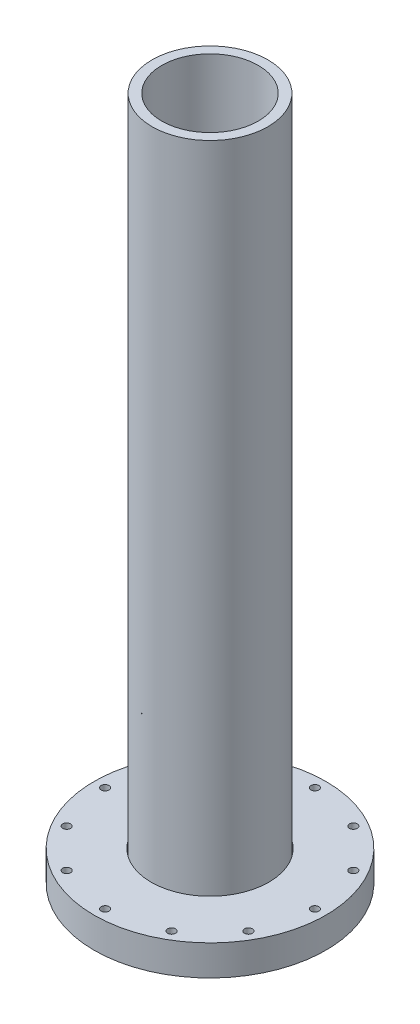
SolidWorks part; units mm, degrees
material "AISI 316 Stainless Steel Sheet (SS)"
ref_plane "Front Plane" through (0, 0, 0) normal (0, 0, 1) x (1, 0, 0)
ref_plane "Top Plane" through (0, 0, 0) normal (0, 1, 0) x (1, 0, 0)
ref_plane "Right Plane" through (0, 0, 0) normal (1, 0, 0) x (0, 0, -1)
sketch "Sketch1" plane through (0, 0, 0) normal (0, 1, 0) x (1, 0, 0)
  circle A0 centre (0, 0) radius 31.75
  circle A1 centre (0, 0) radius 38.1
  dimension "D1" = 63.5
  dimension "D2" = 76.2
extrude "Boss-Extrude1" add sketch "Sketch1" along normal blind 450
sketch "Sketch2" plane through (0, 0, 0) normal (0, 1, 0) x (1, 0, 0)
  circle A0 centre (0, 0) radius 76.2
  circle A3 centre (0, 0) radius 76.2 construction
  circle A4 centre (0, 0) radius 38.6715
  circle A5 centre (0, 0) radius 38.1 construction
  dimension "D1" = 0.5715
extrude "Boss-Extrude2" add sketch "Sketch2" along normal blind 20 separate body
hole_wizard "#6 (0.204) Diameter Hole1" positions "Sketch4" profile "Sketch5" hole size "#6" standard "ANSI Inch" end condition through all
sketch "Sketch4" plane through (0, 0, 0) normal (0, -1, 0) x (-1, 0, 0)
  point P0 (-69, 0)
  dimension "D1" = 69
sketch "Sketch5" plane through (69, 0, 0) normal (1, 0, 0) x (0, 0, -1)
  line L0 (0, 0) -> (0, 450)
  line L1 (0, 450) -> (2.5908, 450)
  line L2 (2.5908, 450) -> (2.5908, 0)
  line L5 (2.5908, 0) -> (0, 0)
  line L11 (0, -6.35) -> (0, 107.95) construction
  dimension "Thru Hole Dia." = 5.1816
  dimension "Thru Hole Depth" = 450
ref_axis "Axis1" through (0, 472.5, 0) along (0, -1, 0)
pattern_circular "CirPattern1" count 12 over 360 about axis through (0, 472.5, 0) along (0, -1, 0) of "#6 (0.204) Diameter Hole1"
sketch "Sketch6" plane through (0, 0, 0) normal (0, -1, 0) x (1, 0, 0)
  circle A0 centre (0, 0) radius 55.14 construction
  circle A1 centre (0, 0) radius 55.14
extrude "Cut-Extrude1" cut sketch "Sketch6" against normal blind 2
equation "\"D1@Sketch2\"=0.045/2"
